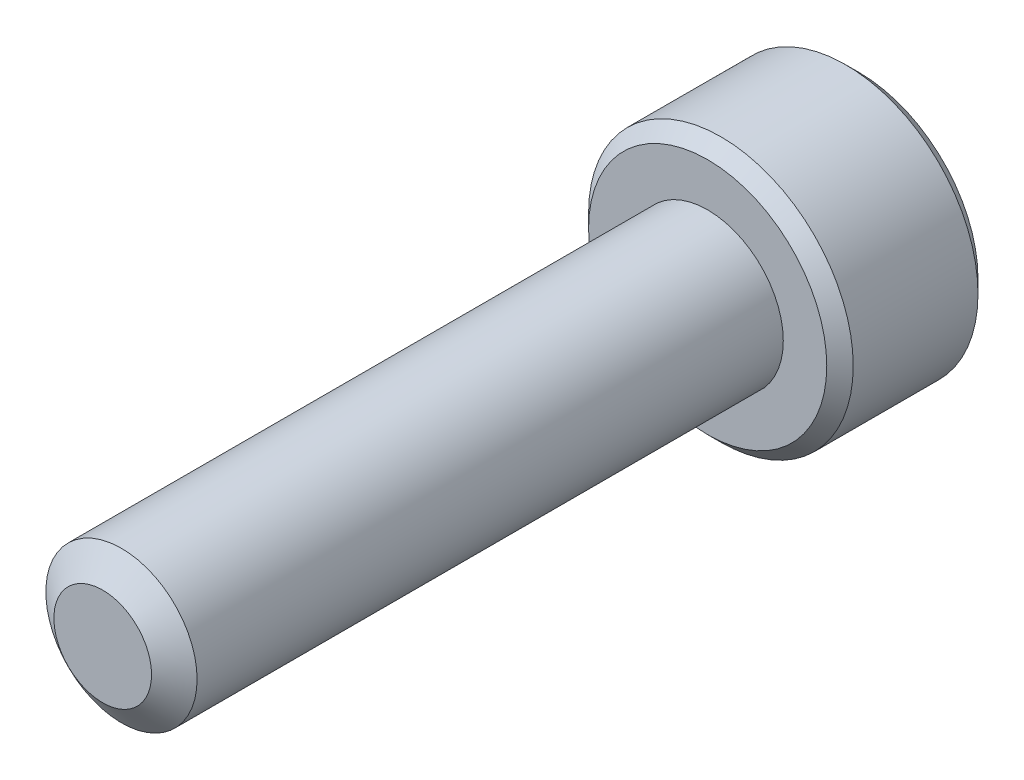
SolidWorks part; units mm, degrees
other "DetailItem1"
material "1.4310 (X10CrNi18-8)"
ref_plane "Front Plane" through (0, 0, 0) normal (0, 0, 1) x (1, 0, 0)
ref_plane "Top Plane" through (0, 0, 0) normal (0, 1, 0) x (1, 0, 0)
ref_plane "Right Plane" through (0, 0, 0) normal (1, 0, 0) x (0, 0, -1)
sketch "Sketch1" plane through (0, 0, 0) normal (0, 0, 1) x (1, 0, 0)
  circle A0 centre (0, 0) radius 2
  dimension "OD" = 4
extrude "Extrude1" add sketch "Sketch1" against normal blind 16
sketch "Sketch2" plane through (0, 0, 0) normal (0, 0, 1) x (1, 0, 0)
  circle A0 centre (0, 0) radius 2 construction
  circle A1 centre (0, 0) radius 2
curve "Helix/Spiral1" pitch 0.7 height 16.7 turns 23.8571 parameters "pitch"=0.7
sketch "Sketch3" plane through (0, 0, 0) normal (1, 0, 0) x (0, 0, -1)
  line L0 (-0.6125, 2) -> (-0.35, 1.5453)
  line L1 (-0.35, 1.5453) -> (-0.2625, 1.5453)
  line L2 (-0.2625, 1.5453) -> (0, 2)
  line L3 (-0.6125, 2) -> (0, 2)
  line L4 (-0.3062, 2) -> (-0.3062, 1.5453) construction
  line L5 (-0.4812, 1.7727) -> (-0.1312, 1.7727) construction
  line L6 (0, 2) -> (0, -2) construction
  dimension "D1" = 0.0875
  dimension "D2" = 0.35
  dimension "D3" = 60
sweep "Cut-Sweep1" [suppressed] cut profiles "Sketch3" path "Helix/Spiral1"
sketch "Sketch4" plane through (0, 0, 0) normal (1, 0, 0) x (0, 0, -1)
  line L0 (0.4962, 2) -> (0, 1.2913)
  line L1 (0, 1.2913) -> (0, 2)
  line L2 (0.4962, 2) -> (0, 2)
  line L3 (-0.6125, 2) -> (0, 2) construction
  line L4 (0, 0) -> (7.0209, 0) construction
  dimension "D1" = 55
  dimension "D2" = 0.254
revolve "Cut-Revolve1" cut sketch "Sketch4" angle 360 about L4
sketch "Sketch6" plane through (0, 0, -16) normal (0, 0, -1) x (-1, 0, 0)
  circle A0 centre (0, 0) radius 3.5
  dimension "head dia" = 7
extrude "Extrude2" add sketch "Sketch6" along normal blind 4
sketch "Sketch7" plane through (0, 0, -20) normal (0, 0, -1) x (-1, 0, 0)
  line L1 (0, 1.7321) -> (-1.5, 0.866)
  line L2 (-1.5, 0.866) -> (-1.5, -0.866)
  line L3 (-1.5, -0.866) -> (0, -1.7321)
  line L4 (0, -1.7321) -> (1.5, -0.866)
  line L5 (1.5, -0.866) -> (1.5, 0.866)
  line L6 (1.5, 0.866) -> (0, 1.7321)
  circle A0 centre (0, 0) radius 1.5 construction
  dimension "hex dia" = 3
extrude "Cut-Extrude1" cut sketch "Sketch7" against normal blind 2.25
sketch "Sketch8" plane through (0, 0, -20) normal (0, 0, -1) x (-1, 0, 0)
  circle A0 centre (0, 0) radius 1.7321
extrude "Cut-Extrude2" cut sketch "Sketch8" against normal through all draft 45
chamfer "Chamfer1" distance 0.35 angle 45 2 edges at (-3.5, 0, -20) (-3.5, 0, -16)
sketch "Sketch10" plane through (0, 0, -16) normal (0, 0, 1) x (1, 0, 0)
  circle A1 centre (0, 0) radius 2
  circle A2 centre (0, 0) radius 2
  dimension "D1" = 0
ref_plane "Plane1" through (0, 0, 0) normal (0, 0, 1) x (1, 0, 0)
extrude "partial thread" [suppressed] add sketch "Sketch10" along normal up to surface (10 mm away) separate body up to plane "Plane1"
chamfer "Chamfer2" [suppressed] distance 0.08 angle 45
combine bodies "Combine1" [suppressed] operation type add bodies to combine 107 108
sketch "Sketch9" plane through (0, 0, 0) normal (1, 0, 0) x (0, 0, -1)
  line L0 (0, 2) -> (0, -2) construction
  line L1 (1.75, 2) -> (1.75, -2) construction
  dimension "D1" = 1.75
equation "\"D3@Helix/Spiral1\" = \"screw length@Extrude1\"+\"pitch@Helix/Spiral1\""
equation "\"D1@Sketch3\" = \"pitch@Helix/Spiral1\"*.125"
equation "\"D2@Sketch3\" = \"pitch@Helix/Spiral1\"*.5"
equation "\"D1@Cut-Extrude1\" = \"hex dia@Sketch7\"*.75"
equation "\"D1@Chamfer1\" = \"head dia@Sketch6\"*.05"
equation "\"D1@Sketch9\" = \"pitch@Helix/Spiral1\"*2.5"
equation "\"D1@Chamfer2\"=\"OD@Sketch1\"*.02"
